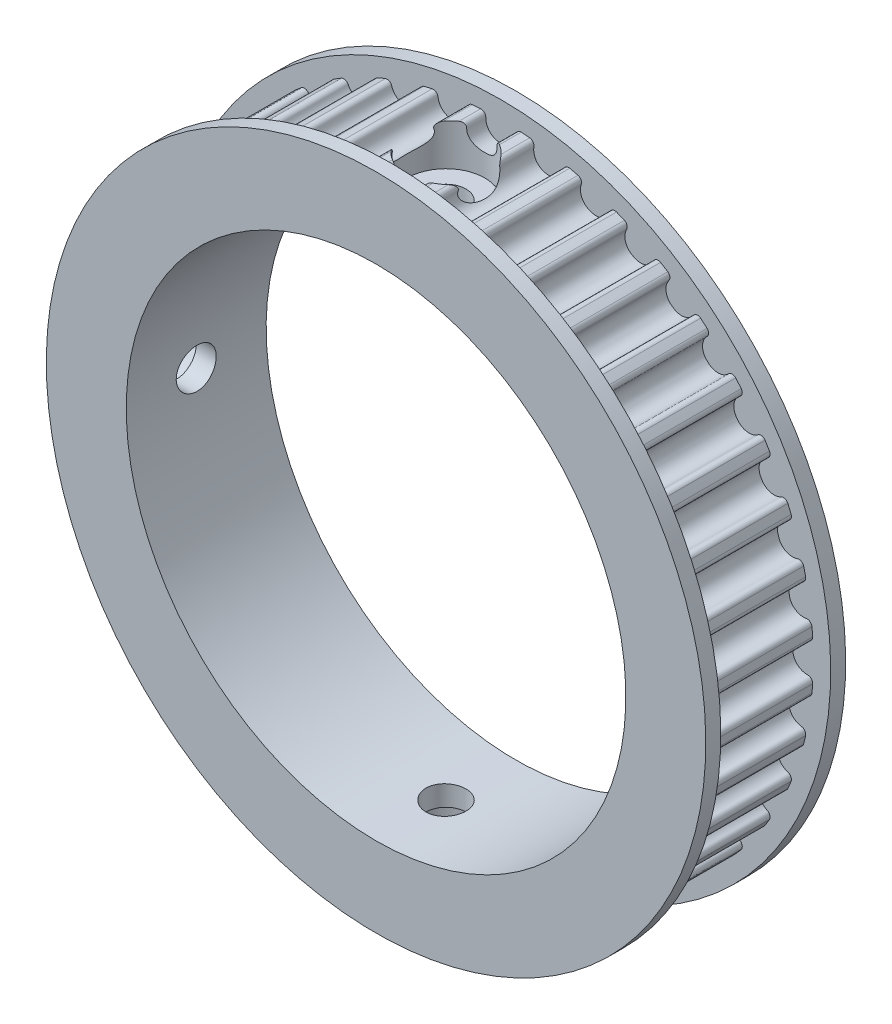
SolidWorks part; units mm, degrees
material "6061 合金"
ref_plane "前视基准面" through (0, 0, 0) normal (0, 0, 1) x (1, 0, 0)
ref_plane "上视基准面" through (0, 0, 0) normal (0, 1, 0) x (1, 0, 0)
ref_plane "右视基准面" through (0, 0, 0) normal (1, 0, 0) x (0, 0, -1)
ref_axis "基准轴1" through (0, 0, 55) along (0, 0, -1)
sketch "旋转草图同步带轮01" plane through (0, 0, 0) normal (1, 0, 0) x (0, 0, -1)
  line L0 (-7, 0) -> (-12.1779, 0) construction
  line L1 (7, 0) -> (7, 33)
  line L2 (7, 33) -> (5.5, 33)
  line L7 (5.5, 33) -> (5.5, 31.2595)
  line L8 (5.5, 31.2595) -> (-5.5, 31.2595)
  line L9 (-5.5, 31.2595) -> (-5.5, 33)
  line L14 (-5.5, 33) -> (-7, 33)
  line L15 (-7, 33) -> (-7, 0)
  line L16 (-7, 0) -> (7, 0)
  dimension "GearBeltOutsideDiameter" = 31.2595
  dimension "D1" = 11
  dimension "D2" = 1.5
  dimension "D3" = 66
revolve "同步带轮01" add sketch "旋转草图同步带轮01" angle 360 about L0
sketch "齿草图同步带轮01" plane through (0, 0, 0) normal (0, 0, 1) x (1, 0, 0)
  arc A0 (31.193, 2.0389) -> (31.193, -2.0389) centre (0, 0) cw
  spline S0 degree 3 poles (31.193, -2.0389) (31.1948, -2.0123) (31.1941, -1.9723) (31.1867, -1.9195) (31.178, -1.8806) (31.1661, -1.8425) (31.1511, -1.8054) (31.1331, -1.7698) (31.1123, -1.7357) (31.0888, -1.7034) (31.0627, -1.6731) (31.0343, -1.6451) (31.0036, -1.6195) (30.971, -1.5965) (30.9365, -1.5763) (30.9006, -1.5589) (30.8633, -1.5445) (30.825, -1.5332) (30.7859, -1.5251) (30.7463, -1.5201) (30.6992, -1.5186) (30.6277, -1.5196) (30.532, -1.516) (30.4198, -1.5026) (30.309, -1.4805) (30.2002, -1.4498) (30.0943, -1.4107) (29.9917, -1.3633) (29.8931, -1.3081) (29.7992, -1.2453) (29.7105, -1.1753) (29.6276, -1.0986) (29.5509, -1.0156) (29.481, -0.9268) (29.4182, -0.8329) (29.363, -0.7343) (29.3157, -0.6317) (29.2767, -0.5257) (29.246, -0.4169) (29.224, -0.3061) (29.2106, -0.1939) (29.2075, -0.1051) (29.2078, -0.0405) (29.2077, 0) (29.2078, 0.0405) (29.2075, 0.1051) (29.2106, 0.1939) (29.224, 0.3061) (29.246, 0.4169) (29.2767, 0.5257) (29.3157, 0.6317) (29.363, 0.7343) (29.4182, 0.8329) (29.481, 0.9268) (29.5509, 1.0156) (29.6276, 1.0986) (29.7105, 1.1753) (29.7992, 1.2453) (29.8931, 1.3081) (29.9917, 1.3633) (30.0943, 1.4107) (30.2002, 1.4498) (30.309, 1.4805) (30.4198, 1.5026) (30.532, 1.516) (30.6277, 1.5196) (30.6992, 1.5186) (30.7463, 1.5201) (30.7859, 1.5251) (30.825, 1.5332) (30.8633, 1.5445) (30.9006, 1.5589) (30.9365, 1.5763) (30.971, 1.5965) (31.0036, 1.6195) (31.0343, 1.6451) (31.0627, 1.6731) (31.0888, 1.7034) (31.1123, 1.7357) (31.1331, 1.7698) (31.1511, 1.8054) (31.1661, 1.8425) (31.178, 1.8806) (31.1867, 1.9195) (31.1941, 1.9723) (31.1948, 2.0123) (31.193, 2.0389) knots 0 0 0 0 0.012476 0.018713 0.024951 0.031189 0.037427 0.043665 0.049903 0.05614 0.062378 0.068616 0.074854 0.081092 0.08733 0.093567 0.099805 0.106043 0.112281 0.118519 0.124756 0.134376 0.152024 0.169672 0.18732 0.204968 0.222616 0.240264 0.257912 0.27556 0.293208 0.310856 0.328503 0.346151 0.363799 0.381447 0.399095 0.416743 0.434391 0.452039 0.469687 0.487335 0.493667 0.5 0.506333 0.512665 0.530313 0.547961 0.565609 0.583257 0.600905 0.618553 0.636201 0.653849 0.671497 0.689144 0.706792 0.72444 0.742088 0.759736 0.777384 0.795032 0.81268 0.830328 0.847976 0.865624 0.875244 0.881481 0.887719 0.893957 0.900195 0.906433 0.91267 0.918908 0.925146 0.931384 0.937622 0.94386 0.950097 0.956335 0.962573 0.968811 0.975049 0.981287 0.987524 1 1 1 1
extrude "齿拉伸切除同步带轮01" cut sketch "齿草图同步带轮01" against normal mid plane 11
pattern_circular "齿形同步带轮01" count 40 every 9 about axis through (0, 0, 55) along (0, 0, -1) of "齿拉伸切除同步带轮01"
sketch "孔旋转草图" plane through (0, 0, 0) normal (1, 0, 0) x (0, 0, -1)
  line L0 (0, 0) -> (1, 0) construction
  line L1 (-7.239, 0) -> (7.239, 0)
  line L2 (7.239, 0) -> (7.239, 25)
  line L3 (7.239, 25) -> (-7.239, 25)
  line L4 (-7.239, 25) -> (-7.239, 0)
  dimension "TaperSide1" = 25
  dimension "TaperSide2" = 25
revolve "孔旋转切除" cut sketch "孔旋转草图" angle 360 about L0
sketch "草图5" plane through (0, 0, 0) normal (0, 1, 0) x (1, 0, 0)
  circle A0 centre (0, 0) radius 2
  dimension "D1" = 4
extrude "切除-拉伸2" cut sketch "草图5" against normal blind 27
sketch "草图6" plane through (0, -27, 0) normal (0, 1, 0) x (1, 0, 0)
  circle A0 centre (0, 0) radius 3.9
  dimension "D1" = 7.8
extrude "切除-拉伸3" cut sketch "草图6" against normal through all
pattern_circular "阵列(圆周)2" count 3 every 90 about axis through (0, 0, 0) along (0, 0, 1) of "切除-拉伸2", "切除-拉伸3" reverse direction yes
